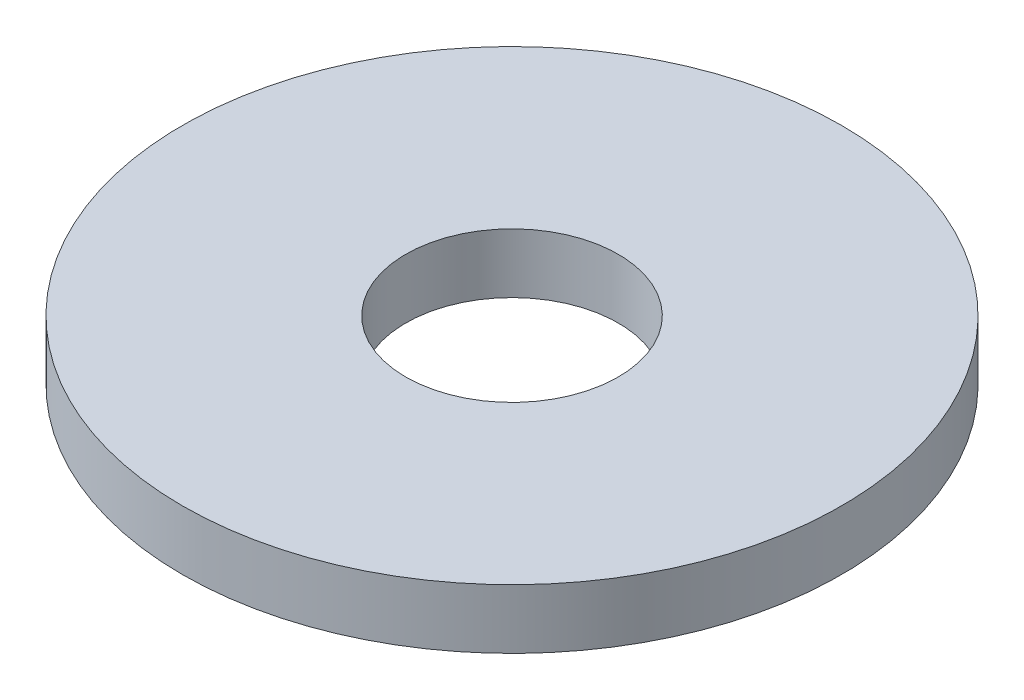
SolidWorks part; units mm, degrees
ref_plane "Front Plane" through (0, 0, 0) normal (0, 0, 1) x (1, 0, 0)
ref_plane "Top Plane" through (0, 0, 0) normal (0, 1, 0) x (1, 0, 0)
ref_plane "Right Plane" through (0, 0, 0) normal (1, 0, 0) x (0, 0, -1)
sketch "Sketch1" plane through (0, 0, 0) normal (0, 1, 0) x (1, 0, 0)
  circle A0 centre (0, 0) radius 77.5
  dimension "FLANGE_OD" = 155
extrude "Boss-Extrude1" add sketch "Sketch1" along normal blind 14
sketch "Sketch2" plane through (0, 0, 0) normal (0, 1, 0) x (1, 0, 0)
  circle A0 centre (0, 0) radius 25
  dimension "BORE_D" = 50
extrude "Cut-Extrude1" cut sketch "Sketch2" along normal through all
sketch "Sketch3" plane through (0, 14, 0) normal (0, 1, 0) x (1, 0, 0)
  circle A0 centre (0, 0) radius 18.5287 construction
  circle A1 centre (-18.5287, 0) radius 5.2758
  dimension "BOLT_D" = 10.5516
  dimension "BOLT_PCD" = 37.0573
extrude "Cut-Extrude2" cut sketch "Sketch3" against normal blind 9.6939 rebuild error yes
pattern_circular "CirPattern1" count 8 over 360 rebuild error yes
